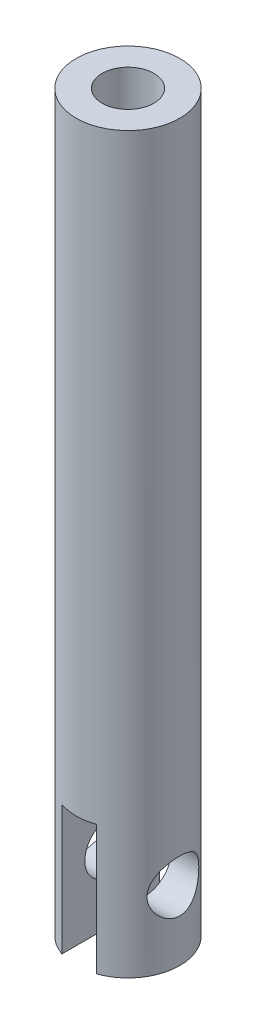
SolidWorks part; units mm, degrees
ref_plane "Front" through (0, 0, 0) normal (0, 0, 1) x (1, 0, 0)
ref_plane "Top" through (0, 0, 0) normal (0, 1, 0) x (1, 0, 0)
ref_plane "Right" through (0, 0, 0) normal (1, 0, 0) x (0, 0, -1)
sketch "Sketch1" plane through (0, 0, 0) normal (0, 1, 0) x (1, 0, 0)
  circle A0 centre (0, 0) radius 6
  circle A1 centre (0, 0) radius 1.5
  dimension "D1" = 12
  dimension "D2" = 3
extrude "Boss-Extrude1" add sketch "Sketch1" along normal blind 75
sketch "Sketch2" plane through (0, 0, 0) normal (0, 0, 1) x (1, 0, 0)
  line L0 (-1657.5786, 28) -> (-1730.2517, 28) construction
  line L1 (-388.9039, 49.5) -> (-461.5771, 49.5) construction
  circle A0 centre (0, 23.5) radius 1.5
  circle A1 centre (0, 54) radius 1.5
  point P8 (-425.2405, 49.5)
  dimension "D1" = 4.5
  dimension "D2" = 4.5
  dimension "D3" = 3
  dimension "D4" = 3
extrude "Cut-Extrude1" cut sketch "Sketch2" against normal blind 75
sketch "Sketch3" plane through (0, 0, 0) normal (0, 0, 1) x (1, 0, 0)
  point P0 (0, 54)
  point P1 (0, 23.5)
sketch "Sketch4" plane through (0, 0, 0) normal (0, -1, 0) x (1, 0, 0)
  circle A0 centre (0, 0) radius 1.5
  circle A1 centre (0, 0) radius 6
  circle A2 centre (0, 0) radius 6
  dimension "D1" = 0
extrude "Boss-Extrude2" add sketch "Sketch4" along normal blind 10
sketch "Sketch5" plane through (0, -10, 0) normal (0, -1, 0) x (1, 0, 0)
  line L0 (-4.3641, 8.1212) -> (8.6932, 3.0707) construction
  line L1 (2, -7.2068) -> (-2, -7.2068)
  line L2 (2, -7.2068) -> (2, 7.2068)
  line L3 (2, 7.2068) -> (-2, 7.2068)
  line L4 (-2, -7.2068) -> (-2, 7.2068)
  line L5 (2, -7.2068) -> (-2, 7.2068) construction
  line L6 (2, 7.2068) -> (-2, -7.2068) construction
  point P0 (0, 0)
  dimension "D1" = 4
extrude "Cut-Extrude2" cut sketch "Sketch5" against normal blind 15
sketch "Sketch7" plane through (-2, 0, 0) normal (1, 0, 0) x (0, 0, -1)
  line L0 (-5.6569, -10) -> (5.6569, -10) construction
  circle A0 centre (0, -2) radius 3
  point P4 (0, -10)
  dimension "D1" = 8
  dimension "D2" = 6
extrude "Cut-Extrude4" cut sketch "Sketch7" against normal blind 15 and the other way blind 15
sketch "Sketch8" plane through (0, 75, 0) normal (0, 1, 0) x (1, 0, 0)
  circle A0 centre (0, 0) radius 3
  dimension "D1" = 6
extrude "Cut-Extrude5" cut sketch "Sketch8" against normal blind 14
